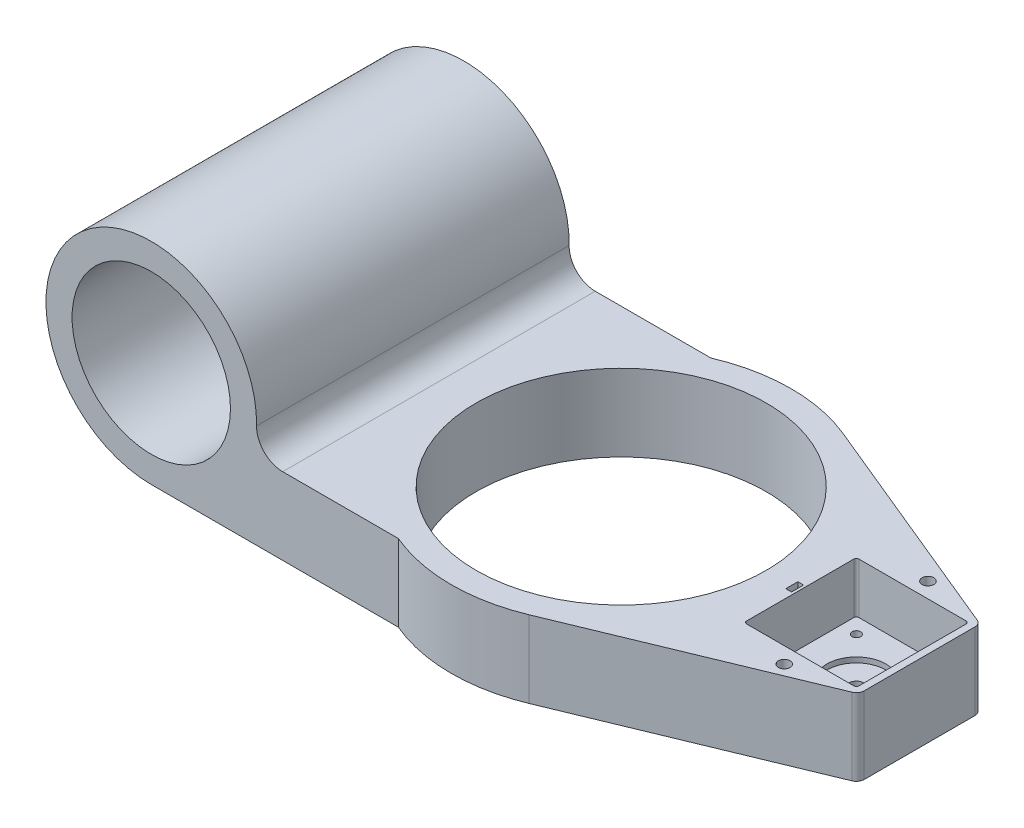
SolidWorks part; units mm, degrees
ref_plane "Front Plane" through (0, 0, 0) normal (0, 0, 1) x (1, 0, 0)
ref_plane "Top Plane" through (0, 0, 0) normal (0, 1, 0) x (1, 0, 0)
ref_plane "Right Plane" through (0, 0, 0) normal (1, 0, 0) x (0, 0, -1)
sketch "Sketch1" plane through (0, 0, 0) normal (0, 1, 0) x (1, 0, 0)
  line L0 (0, 0) -> (90, 0) construction
  line L1 (111.15, -24.15) -> (68.85, -24.15) construction
  line L2 (111.15, 21.15) -> (68.85, 21.15) construction
  line L3 (111.15, 21.15) -> (111.15, -21.15) construction
  line L4 (111.15, -21.15) -> (68.85, -21.15) construction
  line L5 (68.85, 21.15) -> (68.85, -21.15) construction
  line L6 (111.15, 21.15) -> (68.85, -21.15) construction
  line L7 (111.15, -21.15) -> (68.85, 21.15) construction
  line L8 (114.15, 21.15) -> (114.15, -21.15) construction
  line L9 (111.15, 24.15) -> (68.85, 24.15) construction
  line L10 (114.15, 24.15) -> (114.15, -24.15) construction
  line L11 (114.15, 24.15) -> (68.85, 24.15) construction
  line L12 (114.15, -24.15) -> (68.85, -24.15) construction
  line L13 (24.8266, -60.072) -> (112.2958, -23.9226)
  line L14 (112.2958, 23.9226) -> (24.8266, 60.072)
  line L15 (114.15, 21.15) -> (114.15, -21.15)
  circle A0 centre (0, 0) radius 55 construction
  circle A1 centre (0, 0) radius 55.5
  circle A2 centre (0, 0) radius 65 construction
  arc A3 (114.15, 21.15) -> (111.15, 24.15) centre (111.15, 21.15) ccw construction
  arc A4 (114.15, -21.15) -> (111.15, -24.15) centre (111.15, -21.15) cw construction
  arc A5 (114.15, -21.15) -> (112.2958, -23.9226) centre (111.15, -21.15) cw
  arc A6 (112.2958, 23.9226) -> (114.15, 21.15) centre (111.15, 21.15) cw
  arc A7 (24.8266, -60.072) -> (24.8266, 60.072) centre (0, 0) cw
  dimension "D1" = 110
  dimension "D3" = 130
  dimension "D7" = 3
  dimension "D4" = 90
  dimension "D5" = 42.3
  dimension "D2" = 0.5
  dimension "D6" = 3
extrude "Boss-Extrude1" add sketch "Sketch1" along normal blind 29.4
sketch "Sketch2" plane through (0, 29.4, 0) normal (0, 1, 0) x (1, 0, 0)
  line L0 (0, 0) -> (90, 0) construction
  line L2 (69.5, 21.5) -> (110.5, 21.5)
  line L3 (68.5, 20.5) -> (68.5, -20.5)
  line L4 (69.5, -21.5) -> (110.5, -21.5)
  line L5 (111.5, 20.5) -> (111.5, -20.5)
  line L6 (68.5, 21.5) -> (111.5, -21.5) construction
  line L7 (68.5, -21.5) -> (111.5, 21.5) construction
  arc A0 (69.5, 21.5) -> (68.5, 20.5) centre (69.5, 20.5) ccw
  arc A1 (110.5, 21.5) -> (111.5, 20.5) centre (110.5, 20.5) cw
  arc A2 (110.5, -21.5) -> (111.5, -20.5) centre (110.5, -20.5) ccw
  arc A3 (68.5, -20.5) -> (69.5, -21.5) centre (69.5, -20.5) ccw
  dimension "D3" = 1
  dimension "D1" = 90
  dimension "D2" = 43
extrude "Cut-Extrude1" cut sketch "Sketch2" against normal offset from surface (19.4 mm away) 10 up to face at (68.9267, 0, 0)
sketch "Sketch3" plane through (0, 10, 0) normal (0, 1, 0) x (1, 0, 0)
  line L0 (90, 0) -> (0, 0) construction
  line L1 (74.5, 15.5) -> (105.5, 15.5) construction
  line L2 (74.5, 15.5) -> (74.5, -15.5) construction
  line L3 (74.5, -15.5) -> (105.5, -15.5) construction
  line L4 (105.5, 15.5) -> (105.5, -15.5) construction
  line L5 (74.5, 15.5) -> (105.5, -15.5) construction
  line L6 (74.5, -15.5) -> (105.5, 15.5) construction
  circle A0 centre (74.5, -15.5) radius 1.65
  circle A1 centre (105.5, -15.5) radius 1.65
  circle A2 centre (105.5, 15.5) radius 1.65
  circle A3 centre (74.5, 15.5) radius 1.65
  circle A4 centre (90, 0) radius 2.8
  point P0 (90, 0)
  dimension "D2" = 3.3
  dimension "D4" = 5.6
  dimension "D1" = 90
  dimension "D3" = 31
extrude "Cut-Extrude2" cut sketch "Sketch3" against normal through all
sketch "Sketch4" plane through (0, 10, 0) normal (0, 1, 0) x (1, 0, 0)
  circle A0 centre (90, 0) radius 11.3
  dimension "D1" = 22.6
extrude "Cut-Extrude3" cut sketch "Sketch4" against normal blind 2
sketch "Sketch5" plane through (0, 0, 0) normal (0, -1, 0) x (1, 0, 0)
  circle A0 centre (74.5, 15.5) radius 3.3
  circle A1 centre (105.5, 15.5) radius 3.3
  circle A2 centre (74.5, -15.5) radius 3.3
  circle A3 centre (105.5, -15.5) radius 3.3
  dimension "D1" = 6.6
extrude "Cut-Extrude4" cut sketch "Sketch5" against normal blind 5
sketch "Sketch6" plane through (0, 0, 0) normal (0, 0, 1) x (1, 0, 0)
  line L0 (-65, 0) -> (24.8266, 0) construction
  circle A0 centre (-120, 40.3) radius 30.3
  circle A1 centre (-120, 40.3) radius 40.3
  dimension "D1" = 60.6
  dimension "D2" = 10
  dimension "D3" = 120
extrude "Boss-Extrude2" add sketch "Sketch6" along normal mid plane 119.6 separate body
sketch "Sketch7" plane through (0, 0, 59.8) normal (0, 0, 1) x (1, 0, 0)
  line L0 (-65, 29.4) -> (-65, 0)
  line L1 (-65, 0) -> (-120, 0)
  line L2 (-65, 29.4) -> (-81.2021, 29.4)
  circle A0 centre (-120, 40.3) radius 40.3 construction
  arc A1 (-120, 0) -> (-81.2021, 29.4) centre (-120, 40.3) ccw
extrude "Boss-Extrude3" add sketch "Sketch7" against normal up to surface (119.6 mm away) up to face at (-79.7, 40.3, -59.8)
sketch "Sketch8" plane through (0, 29.4, 0) normal (0, 1, 0) x (1, 0, 0)
  line L0 (-65, 59.8) -> (-65, -59.8) construction
  line L1 (-65, 59.8) -> (-65, -59.8)
  line L2 (-65, 59.8) -> (-25.4747, 59.8)
  line L3 (112.2958, 23.9226) -> (24.8266, 60.072)
  line L4 (24.8266, -60.072) -> (112.2958, -23.9226)
  line L5 (114.15, -21.15) -> (114.15, 21.15)
  line L9 (-65, -59.8) -> (-25.4747, -59.8)
  arc A3 (114.15, 21.15) -> (112.2958, 23.9226) centre (111.15, 21.15) ccw
  arc A4 (24.8266, 60.072) -> (24.8266, -60.072) centre (0, 0) ccw
  arc A5 (112.2958, -23.9226) -> (114.15, -21.15) centre (111.15, -21.15) ccw
  arc A7 (-25.4747, 59.8) -> (-25.4747, -59.8) centre (0, 0) ccw
  arc M17 (24.8266, 60.072) -> (24.8266, -60.072) centre (0, 0) ccw
  dimension "D1" = 0
extrude "Boss-Extrude4" add sketch "Sketch8" against normal up to surface (29.4 mm away) contours L1 L9 M17 | L2 L1 M17 region at (-54.1876, 29.4, -45.9003) region at (-54.1876, 29.4, 45.9003) up to face at (105.5, 0, 12.2)
fillet "Fillet1" radius 10 1 edges at (-81.2021, 29.4, 0)
sketch "Sketch9" plane through (0, 29.4, 0) normal (0, 1, 0) x (1, 0, 0)
  line L0 (68.5, 20.5) -> (68.5, -20.5) construction
  line L1 (65.3, 2.3) -> (67.5, 2.3)
  line L2 (65.3, 2.3) -> (65.3, -2.3)
  line L3 (65.3, -2.3) -> (67.5, -2.3)
  line L4 (67.5, 2.3) -> (67.5, -2.3)
  line L5 (65.3, 0) -> (0, 0) construction
  dimension "D1" = 4.6
  dimension "D2" = 2.2
  dimension "D3" = 1
extrude "Cut-Extrude5" cut sketch "Sketch9" against normal blind 11.5
sketch "Sketch10" plane through (0, 29.4, 0) normal (0, 1, 0) x (1, 0, 0)
  line L0 (90, -27.6126) -> (90, 27.3874) construction
  circle A0 centre (90, -27.6126) radius 2.25
  circle A1 centre (90, 27.3874) radius 2.25
  point P5 (90, -0.1126)
  dimension "D2" = 4.5
  dimension "D1" = 55
extrude "Cut-Extrude6" cut sketch "Sketch10" against normal blind 8
